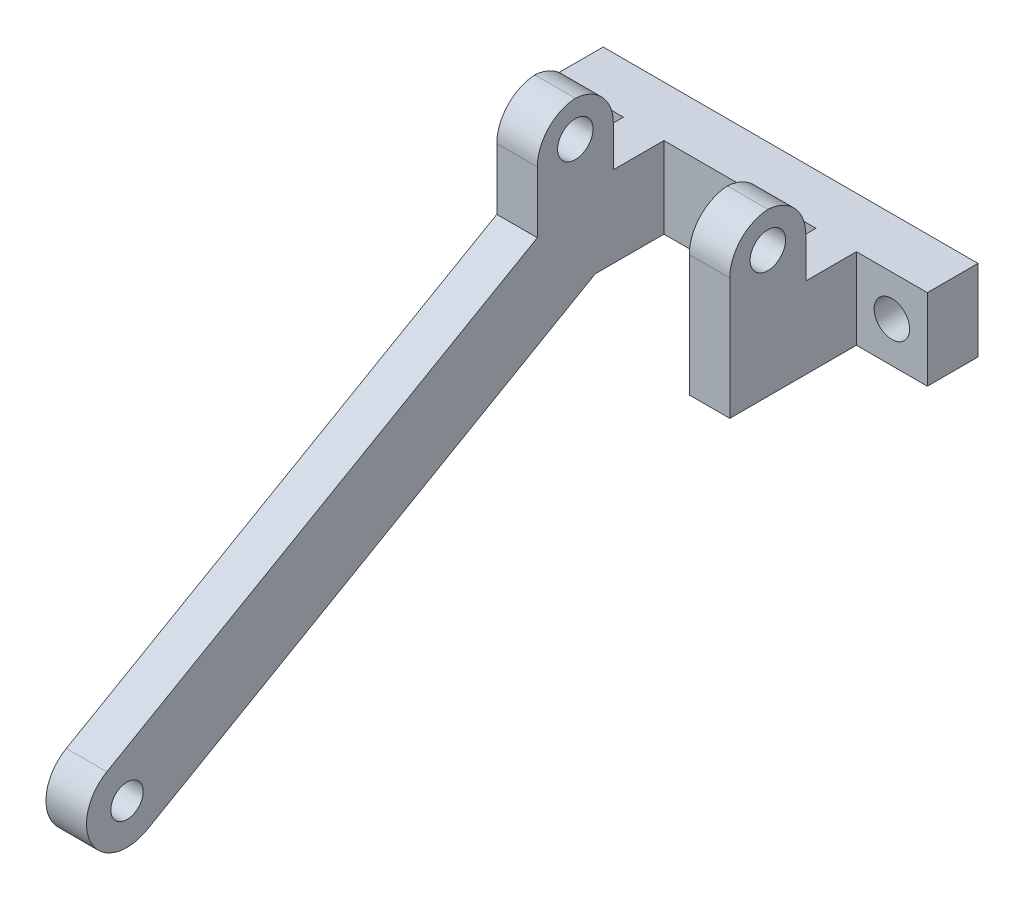
SolidWorks part; units mm, degrees
ref_plane "Front Plane" through (0, 0, 0) normal (0, 0, 1) x (1, 0, 0)
ref_plane "Top Plane" through (0, 0, 0) normal (0, 1, 0) x (1, 0, 0)
ref_plane "Right Plane" through (0, 0, 0) normal (1, 0, 0) x (0, 0, -1)
sketch "Sketch1" plane through (0, 0, 0) normal (0, 0, 1) x (1, 0, 0)
  line L0 (15, 0) -> (-15, 0) construction
  line L1 (-18.5, 4) -> (18.5, 4)
  line L2 (-18.5, 4) -> (-18.5, -4)
  line L3 (-18.5, -4) -> (18.5, -4)
  line L4 (18.5, 4) -> (18.5, -4)
  line L5 (-18.5, 4) -> (18.5, -4) construction
  line L6 (-18.5, -4) -> (18.5, 4) construction
  line L7 (0, -4) -> (0, 4) construction
  circle A0 centre (-15, 0) radius 1.75
  circle A1 centre (15, 0) radius 1.75
  point P0 (0, 0)
  point P12 (0, 0)
  dimension "D3" = 3.5
  dimension "D1" = 37
  dimension "D2" = 8
  dimension "D4" = 15
extrude "Boss-Extrude1" add sketch "Sketch1" along normal blind 5
sketch "Sketch2" plane through (0, 0, 5) normal (0, 0, 1) x (1, 0, 0)
  line L0 (0, 4) -> (0, -4) construction
  line L1 (18.5, 4) -> (-18.5, 4) construction
  line L2 (-18.5, -4) -> (18.5, -4) construction
  line L3 (11.5, -4) -> (7.5, 4) construction
  line L4 (-11.5, 4) -> (-7.5, 4)
  line L5 (-11.5, 4) -> (-11.5, -4)
  line L6 (-11.5, -4) -> (-7.5, -4)
  line L7 (-7.5, 4) -> (-7.5, -4)
  line L8 (-11.5, 4) -> (-7.5, -4) construction
  line L9 (-11.5, -4) -> (-7.5, 4) construction
  line L10 (11.5, 4) -> (7.5, -4) construction
  line L11 (7.5, 4) -> (7.5, -4)
  line L12 (11.5, -4) -> (7.5, -4)
  line L13 (11.5, 4) -> (11.5, -4)
  line L14 (11.5, 4) -> (7.5, 4)
  point P6 (-9.5, 0)
  point P15 (9.5, 0)
  dimension "D1" = 7.5
  dimension "D2" = 4
extrude "Boss-Extrude2" add sketch "Sketch2" along normal blind 12.5
sketch "Sketch4" plane through (0, 4, 0) normal (0, 1, 0) x (1, 0, 0)
  line L0 (-7.5, -17.5) -> (-7.5, -5) construction
  line L1 (-11.5, -17.5) -> (-7.5, -17.5)
  line L2 (-11.5, -17.5) -> (-11.5, -10)
  line L3 (-11.5, -10) -> (-7.5, -10)
  line L4 (-7.5, -17.5) -> (-7.5, -10)
  line L5 (0, 0) -> (0, -5) construction
  line L6 (7.5, -5) -> (-7.5, -5) construction
  line L7 (7.5, -17.5) -> (7.5, -10)
  line L8 (11.5, -10) -> (7.5, -10)
  line L9 (11.5, -17.5) -> (11.5, -10)
  line L10 (11.5, -17.5) -> (7.5, -17.5)
  dimension "D1" = 7.5
extrude "Boss-Extrude3" add sketch "Sketch4" along normal blind 8
sketch "Sketch3" plane through (-11.5, 0, 0) normal (-1, 0, 0) x (0, 0, 1)
  line L0 (10, 8.5) -> (17.5, 8.5) construction
  line L4 (10, 12) -> (10, 4) construction
  line L5 (17.5, 12) -> (17.5, -4) construction
  line L6 (13.75, 8.5) -> (13.75, 12) construction
  line L7 (10, 12) -> (17.5, 12) construction
  circle A0 centre (13.75, 8.5) radius 1.75
  dimension "D1" = 3.5
  dimension "D2" = 8.5
extrude "Cut-Extrude1" cut sketch "Sketch3" against normal through all
fillet "Fillet1" radius 4 4 edges at (-9.5, 12, 10) (9.5, 12, 10) (9.5, 12, 17.5) (-9.5, 12, 17.5)
sketch "Sketch5" plane through (-7.5, 0, 0) normal (1, 0, 0) x (0, 0, -1)
  line L0 (-10, 8) -> (-10, 4) construction
  line L1 (-10, 6.5) -> (-13, 6.5)
  line L2 (-10, 6.5) -> (-10, 1.5)
  line L3 (-10, 1.5) -> (-13, 1.5)
  line L4 (-13, 6.5) -> (-13, 1.5)
  line L5 (-10, 4) -> (-5, 4) construction
  dimension "D1" = 3
  dimension "D2" = 5
  dimension "D3" = 2.5
extrude "Boss-Extrude4" [suppressed] add sketch "Sketch5" along normal up to next
sketch "Sketch6" plane through (-11.5, 0, 0) normal (-1, 0, 0) x (0, 0, 1)
  line L0 (56.0113, -29.4012) -> (11.7824, -4)
  line L1 (17.5, -4) -> (5, -4) construction
  line L2 (11.7824, -4) -> (17.5, 1.9418)
  line L3 (13.75, 8.5) -> (58.0033, -25.9326) construction
  line L4 (17.5, 1.9418) -> (59.9954, -22.4639)
  line L5 (59.9954, -22.4639) -> (56.0113, -29.4012) construction
  line L6 (13.75, 8.5) -> (13.75, -4) construction
  line L7 (17.5, 8) -> (17.5, -4) construction
  circle A0 centre (58.0033, -25.9326) radius 1.6
  arc A1 (56.0113, -29.4012) -> (59.9954, -22.4639) centre (58.0033, -25.9326) ccw
  dimension "D1" = 3.2
  dimension "D2" = 8
  dimension "D3" = 52.114
  dimension "D4" = 56.071
  dimension "D5" = 1.9676
extrude "Boss-Extrude5" add sketch "Sketch6" against normal up to surface (4 mm away) up to face at (-7.5, 6.75, 13.75)
equation "\"X-ROD-SPACING\"=45"
equation "\"Y-ROD-SPACING\"=75"
equation "\"Z-ROD-SPACING\"=17.5"
equation "\"Y-BED-OFFSET\"=2"
equation "\"Y-BED-ROD-INSET\"=3.5"
equation "\"Y-BED-SCREW-SPACING\"=209"
equation "\"Y-BED-SCREW-CUTOUT-SLOT-HEIGHT\"=2"
equation "\"T-SLOT-NUT-FILLET-RADIUS\"=0.5"
equation "\"T-SLOT-SCREW-SHAFT-RADIUS\"=1.55"
equation "\"T-SLOT-SCREW-SHAFT-CUTOUT-LENGTH\"=11.0"
equation "\"T-SLOT-NUT-DEPTH\"=3.5"
equation "\"T-SLOT-NUT-WIDTH\"=2.85"
equation "\"T-SLOT-NUT-END-DISTANCE\"=8"
equation "\"ACRYLIC-THICKNESS\"=10"
equation "\"ACRYLIC-THICKNESS2\"=4.5"
equation "\"ACRYLIC-TAB-CUTOUT-SIZE\"=\"ACRYLIC-THICKNESS\"+\"ACRYLIC-TAB-TOLERANCE\"*2"
equation "\"ACRYLIC-TAB-TOLERANCE\"=-.05"
equation "\"ACRYLIC-TAB-WIDTH\"=\"ACRYLIC-THICKNESS\""
equation "\"ACRYLIC-M3-HOLE\"=2.9"
equation "\"SMOOTHROD-CAP-SCREW-DISTANCE\"=20"
equation "\"FRAME-WIDTH-INNER\"=370"
equation "\"NEMA17-HOLE-SPACING\"=31"
equation "\"NEMA17-CENTRAL-CUTOUT\"=22.5"
equation "\"Z-BRACKET-REACH\"=55"
equation "\"Z-ROD-INSET\"=16"
equation "\"TOP-BRACKET-SPACING\"=40"
equation "\"SMOOTHROD-X-LENGTH\"=350"
equation "\"SMOOTHROD-Y-LENGTH\"=350"
equation "\"SMOOTHROD-Z-LENGTH\"=350"
equation "\"SMOOTHROD-TIGHTENING-HEADROOM\"=.25"
equation "\"LEADSCREW-Z-LENGTH\"=300"
equation "\"SCREW-LENGTH-FRAME\"=\"ACRYLIC-THICKNESS\" + 10"
equation "\"SCREW-LENGTH-MOTOR\"=\"ACRYLIC-THICKNESS\" + 5"
equation "\"SCREW-LENGTH-EXTRUDER\"=28"
equation "\"SCREW-HEAD-RADIUS\"=6"
equation "\"PRINTED-X-SMOOTHROD-DIAMETER\"=9.0"
equation "\"PRINTED-X-SMOOTHROD-CUTOUT\"=10"
equation "\"PRINTED-X-BASE-HEIGHT\"=10"
equation "\"PRINTED-LM8UU-CUTOUT-SIZE\"=15.5"
equation "\"PRINTED-LM8UU-CUTOUT-LENGTH\"=24.5"
equation "\"PRINTED-X-IDLER-HEIGHT\"=16"
equation "\"PSU-MOUNTING-WIDTH\"=95"
equation "\"PSU-MOUNTING-HEIGHT\"=177"
equation "\"Y-BELT-TO-ROD-DISTANCE\"=20"
equation "\"SPOOL-HOLDER-ROD-SPACING\"=150"
equation "\"ACRYLIC-X-CARRIAGE-WIDTH\"=55"
equation "\"ACRYLIC-X-CARRIAGE-HEIGHT\"=75"
equation "\"ACRYLIC-X-CARRIAGE-LM8UU-CUTOUT-WIDTH\"=24.25"
equation "\"ACRYLIC-X-CARRIAGE-LM8UU-CUTOUT-HEIGHT\"=11.0"
equation "\"ACRYLIC-X-CARRIAGE-SCREW-SPACING-X\"=15"
equation "\"ACRYLIC-X-CARRIAGE-SCREW-SPACING-Y\"=33"
equation "\"ACRYLIC-X-CARRIAGE-CENTER-TAB-SPACING\"=14"
equation "\"ACRYLIC-X-CARRIAGE-EXTRUDER-OFFSET\"=26"
equation "\"ACRYLIC-X-CARRIAGE-EXTRUDER-ANGLE\"=90"
equation "\"ACRYLIC-X-CARRIAGE-EXTRUDER-SHELF-DEPTH\"=\"ACRYLIC-X-CARRIAGE-EXTRUDER-OFFSET\" + 28"
equation "\"ACRYLIC-X-CARRIAGE-EXTRUDER-BRACE-SPACING\"=23"
equation "\"ACRYLIC-X-CARRIAGE-EXTRUDER-BRACE-TAB-OFFSET\"=20"
equation "\"ACRYLIC-X-CARRIAGE-EXTRUDER-BRACE-HEIGHT\"=35"
equation "\"ACRYLIC-X-CARRIAGE-EXTRUDER-BRACE-SCREW-SPACING\"=22"
equation "\"ACRYLIC-X-CARRIAGE-DUAL-WIDTH-MULTIPLIER\"=1.65"
equation "\"ACRYLIC-X-CARRIAGE-DUAL-HOTEND-SPACING\"=42"
equation "\"ACRYLIC-X-CARRIAGE-DUAL-WIDTH\"=75"
equation "\"ACRYLIC-X-CARRIAGE-DUAL-HOTEND-SEPARATION\"=36"
equation "\"ACRYLIC-X-CARRIAGE-DUAL-MOUNT-PLATE-DEPTH\"=75"
equation "\"ACRYLIC-X-CARRIAGE-DUAL-MOUNT-BRACE-WIDTH\"=33"
equation "\"ACRYLIC-X-CARRIAGE-DUAL-MOUNT-SCREW-WIDTH\"=40"
equation "\"D3@Sketch1\"=3.5"
equation "\"PRINTED-M3-HOLE\"=3.5"
equation "\"BLOWER-FAN-WIDTH\"=15"
equation "\"D1@Sketch2\"=\"BLOWER-FAN-WIDTH\"/2"
